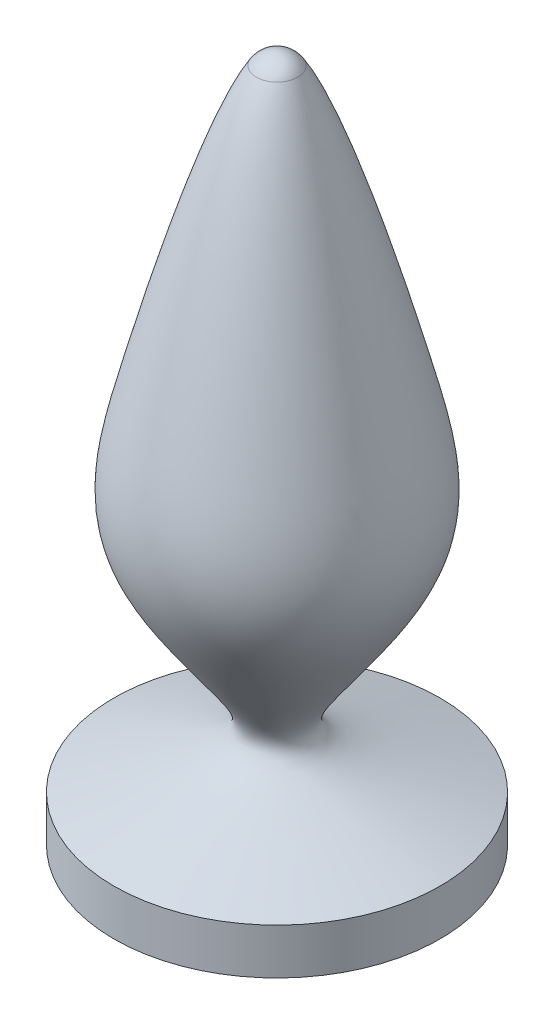
SolidWorks part; units mm, degrees
material "AISI 316 Stainless Steel Sheet (SS)"
ref_plane "Front Plane" through (0, 0, 0) normal (0, 0, 1) x (1, 0, 0)
ref_plane "Top Plane" through (0, 0, 0) normal (0, 1, 0) x (1, 0, 0)
ref_plane "Right Plane" through (0, 0, 0) normal (1, 0, 0) x (0, 0, -1)
sketch "Sketch1" plane through (0, 0, 0) normal (0, 0, 1) x (1, 0, 0)
  line L0 (0, -71.3772) -> (0, 0)
  line L2 (16.9545, -66.6147) -> (16.9545, -71.3772)
  line L3 (16.9545, -71.3772) -> (0, -71.3772)
  arc A0 (2.1447, -1.1792) -> (0, 0) centre (0, -2.54) ccw
  spline S0 degree 3 poles (2.1447, -1.1792) (4.7028, -5.2108) (8.9804, -18.8821) (14.526, -40.9815) (12.2739, -46.216) (1.1426, -61.9245) (0.8084, -60.9479) (16.9545, -66.6147) knots 0.105965 0.105965 0.105965 0.105965 0.448013 0.508175 0.685431 0.718366 1 1 1 1
  dimension "D2" = 3.302
  dimension "D3" = 4.7625
  dimension "D1" = 5.08
  dimension "D4" = 16.9545
  dimension "D5" = 12.7
revolve "Revolve1" add sketch "Sketch1" angle 360 about L0
fillet "Fillet5" [suppressed] radius 0.508
sketch "Sketch9" [suppressed] plane through (0, 0, 0) normal (0, 0, 1) x (1, 0, 0)
  line L0 (0, 0) -> (0, -71.3772)
  line L1 (-17.399, -71.3772) -> (17.399, -71.3772) construction
  line L2 (17.399, -66.9786) -> (17.399, 0)
  line L3 (-17.399, -66.9786) -> (17.399, -66.9786) construction
  line L4 (0, 0) -> (17.399, 0)
  line L5 (13.3859, -65.2593) -> (13.3859, -39.3625)
  line L6 (13.3859, -39.3625) -> (13.3859, 0)
  arc A0 (17.399, -66.9786) -> (17.0543, -66.4975) centre (16.891, -66.9786) ccw construction
  arc A1 (2.1447, -1.1792) -> (-2.1447, -1.1792) centre (0, -2.54) ccw construction
  arc A2 (2.1447, -1.1792) -> (0, 0) centre (0, -2.54) ccw
  spline S0 degree 3 poles (1016.4528, 2761.8004) (40.2905, -74.737) (28.6858, -70.4456) (16.4956, -66.3079) (15.6352, -66.0169) (14.4859, -65.6297) (13.5033, -65.299) (12.6028, -64.9954) (11.7786, -64.7163) (11.0431, -64.4654) (10.3733, -64.2347) (9.7661, -64.0231) (9.203, -63.8239) (8.6784, -63.6349) (8.1808, -63.4517) (7.7188, -63.2774) (7.2801, -63.1069) (6.8944, -62.952) (6.5489, -62.8083) (6.2392, -62.6748) (5.9442, -62.5423) (5.6647, -62.4111) (5.4083, -62.2845) (5.1843, -62.1679) (4.9891, -62.0608) (4.8083, -61.9565) (4.6317, -61.8483) (4.4618, -61.737) (4.3066, -61.6275) (4.1673, -61.5214) (4.0427, -61.4185) (3.9294, -61.3167) (3.8224, -61.2112) (3.7197, -61.0988) (3.6251, -60.9813) (3.5404, -60.8598) (3.4733, -60.7469) (3.4159, -60.6326) (3.3725, -60.5288) (3.3376, -60.4253) (3.3094, -60.3212) (3.2864, -60.2042) (3.2716, -60.0749) (3.2666, -59.9443) (3.2708, -59.8136) (3.2836, -59.6821) (3.3049, -59.5476) (3.3345, -59.4106) (3.3741, -59.2634) (3.4252, -59.1045) (3.4885, -58.935) (3.5621, -58.7603) (3.6459, -58.5793) (3.7412, -58.3899) (3.8472, -58.1932) (3.9606, -57.9943) (4.0815, -57.792) (4.2194, -57.57) (4.3762, -57.3267) (4.5518, -57.0627) (4.7371, -56.7912) (4.9464, -56.4905) (5.1831, -56.1563) (5.4476, -55.7877) (5.7267, -55.4021) (6.0197, -54.999) (6.3486, -54.5468) (6.6412, -54.1435) (6.9823, -53.671) (7.3509, -53.1571) (7.7975, -52.5281) (8.2191, -51.9275) (8.5951, -51.3854) (8.9762, -50.8289) (9.3586, -50.2612) (9.7555, -49.658) (10.137, -49.0622) (10.5132, -48.4541) (10.8768, -47.8408) (11.2167, -47.2376) (11.533, -46.6422) (11.8258, -46.0517) (12.094, -45.4655) (12.3241, -44.9139) (12.5202, -44.3953) (12.6845, -43.9144) (12.8275, -43.4458) (12.9506, -42.9897) (13.0607, -42.522) (13.1576, -42.0349) (13.2385, -41.5342) (13.3019, -41.0275) (13.3508, -40.4841) (13.382, -39.8826) (13.3896, -39.2398) (13.3717, -38.5597) (13.327, -37.8504) (13.2557, -37.1294) (13.1851, -36.5861) (13.1162, -36.1173) (13.0482, -35.695) (12.952, -35.1551) (12.8428, -34.5906) (12.716, -33.9788) (12.568, -33.3066) (12.3911, -32.5441) (12.1909, -31.719) (11.9714, -30.8448) (11.7912, -30.1434) (11.3533, -28.4531) (10.822, -26.4429) (10.1329, -23.9126) (9.6167, -22.0565) (9.109, -20.2709) (8.6295, -18.621) (8.1649, -17.057) (7.71, -15.5604) (7.2702, -14.1481) (6.8552, -12.8481) (6.4697, -11.67) (6.1072, -10.5899) (5.7713, -9.6142) (5.4498, -8.7036) (5.138, -7.8443) (4.8389, -7.0434) (4.5553, -6.3063) (4.2946, -5.6491) (4.05, -5.0515) (3.8231, -4.514) (3.6023, -4.0079) (3.3953, -3.5497) (3.1997, -3.1321) (3.0195, -2.7609) (2.849, -2.4229) (2.6876, -2.1151) (2.5399, -1.8446) (2.401, -1.6006) (2.303, -1.4353) (2.2384, -1.3293) (2.2071, -1.2786) (-1.5226, 4.7074) (-12.3682, 6.1964) (2530.3734, 1612.9827) knots -0.467804 -0.467804 -0.467804 -0.467804 0.000052 0.001589 0.020751 0.034522 0.047614 0.060097 0.070588 0.080637 0.08959 0.097474 0.10504 0.112258 0.118636 0.125162 0.130998 0.136499 0.140935 0.1452 0.149297 0.153207 0.156918 0.160151 0.162788 0.165367 0.168073 0.170648 0.173075 0.17528 0.177293 0.179204 0.181062 0.182991 0.18498 0.186784 0.188608 0.189962 0.191634 0.192874 0.194107 0.195723 0.197395 0.199044 0.200678 0.202356 0.204055 0.205844 0.207673 0.209841 0.212176 0.214536 0.217035 0.219745 0.222583 0.225512 0.228436 0.231526 0.235429 0.239423 0.243556 0.247904 0.253326 0.259099 0.265121 0.271392 0.278013 0.286341 0.290299 0.300133 0.310338 0.319578 0.327981 0.335376 0.345177 0.353957 0.362776 0.372027 0.381093 0.389833 0.398304 0.406677 0.414844 0.422763 0.429357 0.435885 0.442046 0.447948 0.453811 0.46028 0.466792 0.473056 0.479657 0.487494 0.49591 0.504049 0.51331 0.522877 0.53154 0.534103 0.540858 0.547775 0.554913 0.562677 0.571487 0.581035 0.592384 0.603709 0.615242 0.619865 0.669975 0.694153 0.71939 0.743088 0.764604 0.784599 0.805004 0.82397 0.840734 0.856795 0.871012 0.88397 0.895957 0.907662 0.918661 0.928401 0.937636 0.945495 0.952904 0.959778 0.966451 0.971982 0.977279 0.982112 0.986346 0.990471 0.993807 0.997002 0.997764 0.998518 0.999263 1.265425 1.265425 1.265425 1.265425 only from (17.0543, -66.4975) to (2.1447, -1.1792) construction
  spline S1 degree 3 poles (17.0543, -66.4975) (16.5761, -66.3352) (15.7521, -66.0564) (14.599, -65.6678) (13.8731, -65.4235) (13.4932, -65.2955) (13.442, -65.2783) knots 0 0 0 0 0.019165 0.033015 0.04618 0.04823 0.04823 0.04823 0.04823
  spline S3 degree 3 poles (13.3859, -39.3625) (13.3859, -39.1047) (13.3744, -38.6029) (13.327, -37.8504) (13.2557, -37.1294) (13.1851, -36.5861) (13.1162, -36.1173) (13.0482, -35.695) (12.952, -35.1551) (12.8428, -34.5906) (12.716, -33.9788) (12.568, -33.3066) (12.3911, -32.5441) (12.1909, -31.719) (11.9714, -30.8448) (11.7912, -30.1434) (11.3533, -28.4531) (10.822, -26.4429) (10.1329, -23.9126) (9.6167, -22.0565) (9.109, -20.2709) (8.6295, -18.621) (8.1649, -17.057) (7.71, -15.5604) (7.2702, -14.1481) (6.8552, -12.8481) (6.4697, -11.67) (6.1072, -10.5899) (5.7713, -9.6142) (5.4498, -8.7036) (5.138, -7.8443) (4.8389, -7.0434) (4.5553, -6.3063) (4.2946, -5.6491) (4.05, -5.0515) (3.8231, -4.514) (3.6023, -4.0079) (3.3953, -3.5497) (3.1997, -3.1321) (3.0195, -2.7609) (2.849, -2.4229) (2.6876, -2.1151) (2.5399, -1.8446) (2.401, -1.6006) (2.303, -1.4353) (2.2384, -1.3293) (2.2071, -1.2786) (2.1759, -1.2286) (2.1551, -1.1956) (2.1447, -1.1792) knots 0.494266 0.494266 0.494266 0.494266 0.504049 0.51331 0.522877 0.53154 0.534103 0.540858 0.547775 0.554913 0.562677 0.571487 0.581035 0.592384 0.603709 0.615242 0.619865 0.669975 0.694153 0.71939 0.743088 0.764604 0.784599 0.805004 0.82397 0.840734 0.856795 0.871012 0.88397 0.895957 0.907662 0.918661 0.928401 0.937636 0.945495 0.952904 0.959778 0.966451 0.971982 0.977279 0.982112 0.986346 0.990471 0.993807 0.997002 0.997764 0.998518 0.999263 1 1 1 1
  point P18 (13.3859, -39.3625)
  point P20 (13.3859, -65.2593)
sketch "Sketch8" plane through (0, 0, 0) normal (0, 0, 1) x (1, 0, 0)
  line L0 (0, 97.852) -> (0, -97.852)
  line L1 (0, -97.852) -> (-27.3156, -97.852)
  line L2 (-27.3156, -97.852) -> (-27.3156, 97.852)
  line L3 (-27.3156, 97.852) -> (0, 97.852)
  point P4 (0, 0)
extrude "Cut-Extrude4" [suppressed] cut sketch "Sketch8" against normal blind 25.4 and the other way blind 25.4
sketch "Sketch11" [suppressed] plane through (0, 0, 0) normal (0, 0, 1) x (1, 0, 0)
  line L5 (13.3859, -65.2593) -> (13.3859, -39.3625)
  spline S2 degree 3 poles (13.442, -65.2783) (13.0798, -65.1562) (12.4576, -64.9464) (11.5853, -64.6505) (10.8581, -64.402) (10.1979, -64.1739) (9.6023, -63.9654) (9.0448, -63.7673) (8.5198, -63.577) (8.0256, -63.3937) (7.5695, -63.22) (7.1428, -63.0524) (6.7634, -62.8982) (6.424, -62.7551) (6.119, -62.6215) (5.8306, -62.4897) (5.5602, -62.3603) (5.3115, -62.2349) (5.0934, -62.1188) (4.898, -62.009) (4.7186, -61.9023) (4.545, -61.7925) (4.3815, -61.6814) (4.2343, -61.5735) (4.1029, -61.4693) (3.9849, -61.3677) (3.8762, -61.2655) (3.771, -61.1566) (3.6722, -61.0418) (3.5815, -60.921) (3.509, -60.8088) (3.4516, -60.7052) (3.402, -60.6016) (3.3612, -60.498) (3.3285, -60.3942) (3.3024, -60.2895) (3.2817, -60.1718) (3.2694, -60.0422) (3.2668, -59.9116) (3.2732, -59.781) (3.2882, -59.6488) (3.3116, -59.5135) (3.3432, -59.3757) (3.3855, -59.2254) (3.4395, -59.064) (3.5059, -58.8919) (3.582, -58.7158) (3.6687, -58.5327) (3.7669, -58.3411) (3.8748, -58.1438) (3.9902, -57.9441) (4.1128, -57.7409) (4.2525, -57.5181) (4.4109, -57.2739) (4.5879, -57.0093) (4.7754, -56.7357) (4.987, -56.4327) (5.2263, -56.0957) (5.493, -55.7248) (5.7744, -55.3363) (6.0698, -54.9301) (6.3829, -54.4996) (6.6586, -54.1194) (6.9823, -53.671) (7.3509, -53.1571) (7.7975, -52.5281) (8.2191, -51.9275) (8.5951, -51.3854) (8.9762, -50.8289) (9.3586, -50.2612) (9.7555, -49.658) (10.137, -49.0622) (10.5132, -48.4541) (10.8768, -47.8408) (11.2167, -47.2376) (11.533, -46.6422) (11.8258, -46.0517) (12.094, -45.4655) (12.3241, -44.9139) (12.5202, -44.3953) (12.6845, -43.9144) (12.8275, -43.4458) (12.9506, -42.9897) (13.0607, -42.522) (13.1576, -42.0349) (13.2385, -41.5342) (13.3019, -41.0275) (13.3508, -40.4841) (13.3798, -39.9259) (13.3859, -39.5409) (13.3859, -39.3625) knots 0.04823 0.04823 0.04823 0.04823 0.062735 0.073149 0.08319 0.091898 0.099658 0.107139 0.114352 0.12085 0.127141 0.132875 0.138247 0.142684 0.146854 0.150885 0.154715 0.158231 0.161456 0.164092 0.166737 0.169376 0.171887 0.174234 0.176302 0.178254 0.180143 0.181963 0.183996 0.18589 0.18769 0.189062 0.190383 0.192048 0.193285 0.194511 0.19614 0.197816 0.199449 0.201094 0.202776 0.204496 0.206301 0.20814 0.210421 0.212756 0.215143 0.217701 0.220442 0.223314 0.226231 0.229197 0.232319 0.236213 0.240244 0.244398 0.2488 0.254269 0.260086 0.266136 0.272476 0.279145 0.286341 0.290299 0.300133 0.310338 0.319578 0.327981 0.335376 0.345177 0.353957 0.362776 0.372027 0.381093 0.389833 0.398304 0.406677 0.414844 0.422763 0.429357 0.435885 0.442046 0.447948 0.453811 0.46028 0.466792 0.473056 0.479657 0.487494 0.494266 0.494266 0.494266 0.494266
  point P18 (13.3859, -39.3625)
  point P20 (13.3859, -65.2593)
sketch "Sketch12" [suppressed] plane through (0, 0, 0) normal (0, 0, 1) x (1, 0, 0)
  line L0 (0, 0) -> (0, -71.3772)
  line L2 (17.399, -66.9786) -> (17.399, 0)
  line L4 (0, 0) -> (17.399, 0)
  line L5 (13.3859, -65.2593) -> (13.3859, -39.3625)
  line L6 (13.3859, -39.3625) -> (13.3859, 0)
  arc A2 (2.1447, -1.1792) -> (0, 0) centre (0, -2.54) ccw
  spline S1 degree 3 poles (17.0543, -66.4975) (16.5761, -66.3352) (15.7521, -66.0564) (14.599, -65.6678) (13.8731, -65.4235) (13.4932, -65.2955) (13.442, -65.2783) knots 0 0 0 0 0.019165 0.033015 0.04618 0.04823 0.04823 0.04823 0.04823
  spline S2 degree 3 poles (13.442, -65.2783) (13.0798, -65.1562) (12.4576, -64.9464) (11.5853, -64.6505) (10.8581, -64.402) (10.1979, -64.1739) (9.6023, -63.9654) (9.0448, -63.7673) (8.5198, -63.577) (8.0256, -63.3937) (7.5695, -63.22) (7.1428, -63.0524) (6.7634, -62.8982) (6.424, -62.7551) (6.119, -62.6215) (5.8306, -62.4897) (5.5602, -62.3603) (5.3115, -62.2349) (5.0934, -62.1188) (4.898, -62.009) (4.7186, -61.9023) (4.545, -61.7925) (4.3815, -61.6814) (4.2343, -61.5735) (4.1029, -61.4693) (3.9849, -61.3677) (3.8762, -61.2655) (3.771, -61.1566) (3.6722, -61.0418) (3.5815, -60.921) (3.509, -60.8088) (3.4516, -60.7052) (3.402, -60.6016) (3.3612, -60.498) (3.3285, -60.3942) (3.3024, -60.2895) (3.2817, -60.1718) (3.2694, -60.0422) (3.2668, -59.9116) (3.2732, -59.781) (3.2882, -59.6488) (3.3116, -59.5135) (3.3432, -59.3757) (3.3855, -59.2254) (3.4395, -59.064) (3.5059, -58.8919) (3.582, -58.7158) (3.6687, -58.5327) (3.7669, -58.3411) (3.8748, -58.1438) (3.9902, -57.9441) (4.1128, -57.7409) (4.2525, -57.5181) (4.4109, -57.2739) (4.5879, -57.0093) (4.7754, -56.7357) (4.987, -56.4327) (5.2263, -56.0957) (5.493, -55.7248) (5.7744, -55.3363) (6.0698, -54.9301) (6.3829, -54.4996) (6.6586, -54.1194) (6.9823, -53.671) (7.3509, -53.1571) (7.7975, -52.5281) (8.2191, -51.9275) (8.5951, -51.3854) (8.9762, -50.8289) (9.3586, -50.2612) (9.7555, -49.658) (10.137, -49.0622) (10.5132, -48.4541) (10.8768, -47.8408) (11.2167, -47.2376) (11.533, -46.6422) (11.8258, -46.0517) (12.094, -45.4655) (12.3241, -44.9139) (12.5202, -44.3953) (12.6845, -43.9144) (12.8275, -43.4458) (12.9506, -42.9897) (13.0607, -42.522) (13.1576, -42.0349) (13.2385, -41.5342) (13.3019, -41.0275) (13.3508, -40.4841) (13.3798, -39.9259) (13.3859, -39.5409) (13.3859, -39.3625) knots 0.04823 0.04823 0.04823 0.04823 0.062735 0.073149 0.08319 0.091898 0.099658 0.107139 0.114352 0.12085 0.127141 0.132875 0.138247 0.142684 0.146854 0.150885 0.154715 0.158231 0.161456 0.164092 0.166737 0.169376 0.171887 0.174234 0.176302 0.178254 0.180143 0.181963 0.183996 0.18589 0.18769 0.189062 0.190383 0.192048 0.193285 0.194511 0.19614 0.197816 0.199449 0.201094 0.202776 0.204496 0.206301 0.20814 0.210421 0.212756 0.215143 0.217701 0.220442 0.223314 0.226231 0.229197 0.232319 0.236213 0.240244 0.244398 0.2488 0.254269 0.260086 0.266136 0.272476 0.279145 0.286341 0.290299 0.300133 0.310338 0.319578 0.327981 0.335376 0.345177 0.353957 0.362776 0.372027 0.381093 0.389833 0.398304 0.406677 0.414844 0.422763 0.429357 0.435885 0.442046 0.447948 0.453811 0.46028 0.466792 0.473056 0.479657 0.487494 0.494266 0.494266 0.494266 0.494266
  spline S3 degree 3 poles (13.3859, -39.3625) (13.3859, -39.1047) (13.3744, -38.6029) (13.327, -37.8504) (13.2557, -37.1294) (13.1851, -36.5861) (13.1162, -36.1173) (13.0482, -35.695) (12.952, -35.1551) (12.8428, -34.5906) (12.716, -33.9788) (12.568, -33.3066) (12.3911, -32.5441) (12.1909, -31.719) (11.9714, -30.8448) (11.7912, -30.1434) (11.3533, -28.4531) (10.822, -26.4429) (10.1329, -23.9126) (9.6167, -22.0565) (9.109, -20.2709) (8.6295, -18.621) (8.1649, -17.057) (7.71, -15.5604) (7.2702, -14.1481) (6.8552, -12.8481) (6.4697, -11.67) (6.1072, -10.5899) (5.7713, -9.6142) (5.4498, -8.7036) (5.138, -7.8443) (4.8389, -7.0434) (4.5553, -6.3063) (4.2946, -5.6491) (4.05, -5.0515) (3.8231, -4.514) (3.6023, -4.0079) (3.3953, -3.5497) (3.1997, -3.1321) (3.0195, -2.7609) (2.849, -2.4229) (2.6876, -2.1151) (2.5399, -1.8446) (2.401, -1.6006) (2.303, -1.4353) (2.2384, -1.3293) (2.2071, -1.2786) (2.1759, -1.2286) (2.1551, -1.1956) (2.1447, -1.1792) knots 0.494266 0.494266 0.494266 0.494266 0.504049 0.51331 0.522877 0.53154 0.534103 0.540858 0.547775 0.554913 0.562677 0.571487 0.581035 0.592384 0.603709 0.615242 0.619865 0.669975 0.694153 0.71939 0.743088 0.764604 0.784599 0.805004 0.82397 0.840734 0.856795 0.871012 0.88397 0.895957 0.907662 0.918661 0.928401 0.937636 0.945495 0.952904 0.959778 0.966451 0.971982 0.977279 0.982112 0.986346 0.990471 0.993807 0.997002 0.997764 0.998518 0.999263 1 1 1 1
  point P18 (13.3859, -39.3625)
  point P20 (13.3859, -65.2593)
sketch "Sketch7" [suppressed] plane through (0, 0, 0) normal (0, 0, 1) x (1, 0, 0)
  line L0 (0, 36.2888) -> (0, -36.443)
  line L1 (0, -36.443) -> (16.7485, -36.443)
  spline S3 degree 3 poles (16.7485, -36.443) (16.6964, -36.421) (16.1852, -36.2034) (14.7412, -35.5632) (12.3997, -34.3922) (9.52, -32.6081) (7.0407, -30.5489) (5.1322, -28.2141) (3.8773, -26.0184) (3.0367, -23.4156) (2.8006, -20.7092) (3.0825, -18.2479) (3.8584, -15.442) (5.1532, -12.6994) (6.7245, -10.0601) (8.1892, -7.7756) (9.4485, -5.7298) (10.397, -3.9042) (10.9183, -2.4334) (11.2269, -0.7681) (11.2961, 1.0712) (11.0861, 3.7785) (10.3136, 7.5197) (8.8894, 12.4167) (7.3232, 17.3646) (5.6401, 22.2719) (3.8492, 27.1382) (2.2643, 31.1313) (1.0083, 34.0755) (0.3568, 35.5233) (0.0436, 36.1956) (0, 36.2888) knots 0.013851 0.013851 0.013851 0.013851 0.015625 0.03125 0.0625 0.09375 0.125 0.140625 0.15625 0.171875 0.1875 0.203125 0.21875 0.25 0.28125 0.3125 0.34375 0.375 0.40625 0.4375 0.46875 0.5 0.5625 0.625 0.6875 0.75 0.8125 0.875 0.90625 0.93044 0.934346 0.934346 0.934346 0.934346
